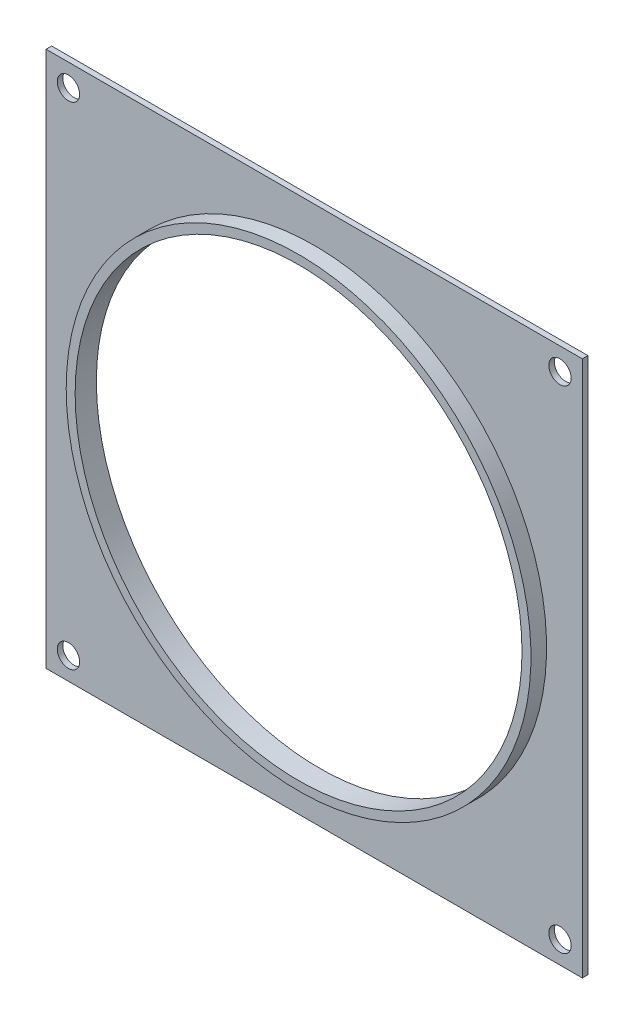
SolidWorks part; units mm, degrees
material "Alloy Steel"
ref_plane "Front Plane" through (0, 0, 0) normal (0, 0, 1) x (1, 0, 0)
ref_plane "Top Plane" through (0, 0, 0) normal (0, 1, 0) x (1, 0, 0)
ref_plane "Right Plane" through (0, 0, 0) normal (1, 0, 0) x (0, 0, -1)
sketch "Sketch1" plane through (0, 0, 0) normal (0, 0, 1) x (1, 0, 0)
  line L0 (0, 0) -> (0, 89.8417) construction
  line L1 (0, 0) -> (85.093, 0) construction
  line L2 (-76.2, 76.2) -> (76.2, 76.2)
  line L3 (76.2, 76.2) -> (76.2, -76.2)
  line L4 (-76.2, 76.2) -> (-76.2, -76.2)
  line L5 (-76.2, -76.2) -> (76.2, -76.2)
  circle A0 centre (0, 0) radius 63.5
  point P10 (0, 76.2)
  point P11 (-76.2, 0)
  point P12 (76.2, 0)
  dimension "D1" = 127
  dimension "D2" = 152.4
  dimension "D3" = 152.4
extrude "Boss-Extrude1" add sketch "Sketch1" along normal blind 1.5875
sketch "Sketch2" plane through (0, 0, 1.5875) normal (0, 0, 1) x (1, 0, 0)
  circle A0 centre (0, 0) radius 66.04
  circle A1 centre (0, 0) radius 63.5 construction
  circle A2 centre (0, 0) radius 63.5
  dimension "D1" = 2.54
extrude "Boss-Extrude2" add sketch "Sketch2" along normal offset from surface (4.445 mm away) 6.0325 up to face at (0, 0, 0)
sketch "Sketch3" plane through (0, 0, 1.5875) normal (0, 0, 1) x (1, 0, 0)
  line L0 (0, 0) -> (0, -106.5116) construction
  line L1 (0, 0) -> (138.2793, 0) construction
  line L2 (-76.2, -76.2) -> (76.2, -76.2) construction
  line L3 (76.2, -76.2) -> (76.2, 76.2) construction
  circle A0 centre (69.85, -69.85) radius 3.175
  circle A1 centre (-69.85, -69.85) radius 3.175
  circle A2 centre (-69.85, 69.85) radius 3.175
  circle A3 centre (69.85, 69.85) radius 3.175
  dimension "D3" = 6.35
  dimension "D1" = 6.35
  dimension "D2" = 6.35
extrude "Cut-Extrude1" cut sketch "Sketch3" against normal up to surface (1.5875 mm away) up to face at (0, 0, 0)
